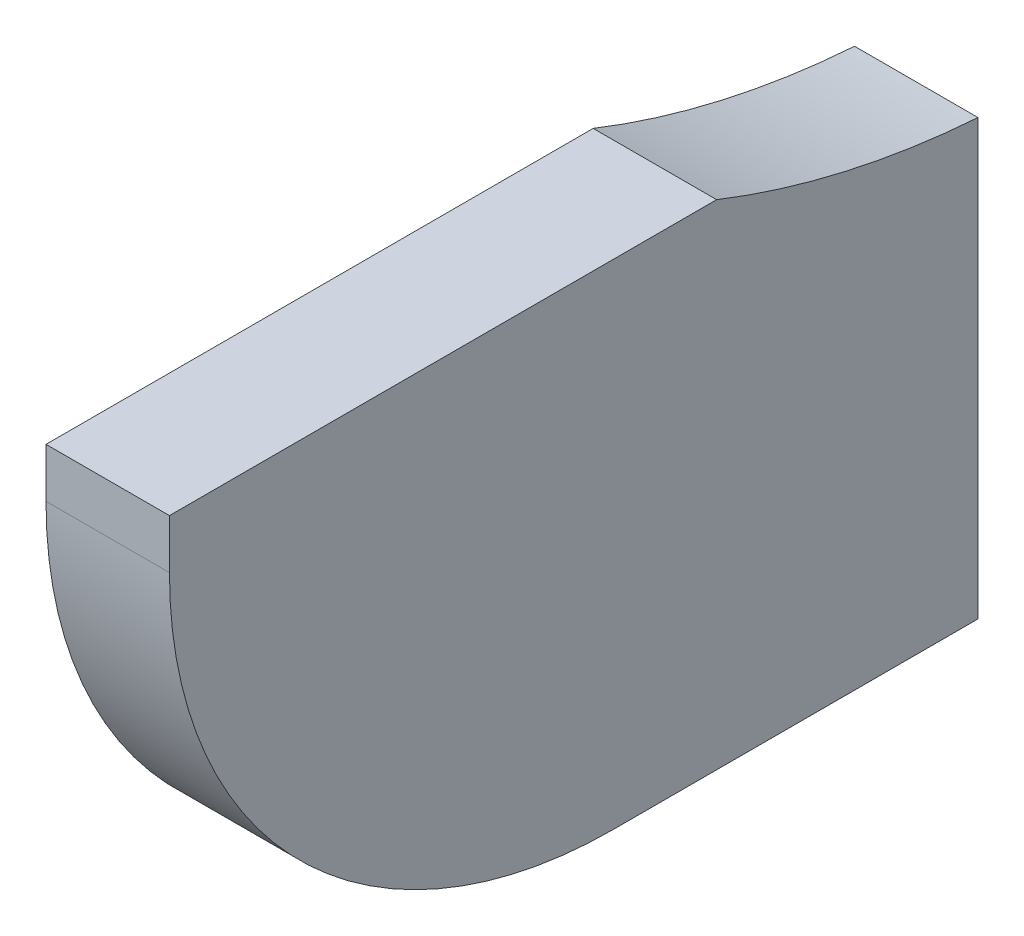
SolidWorks part; units mm, degrees
ref_plane "Front Plane" through (0, 0, 0) normal (0, 0, 1) x (1, 0, 0)
ref_plane "Top Plane" through (0, 0, 0) normal (0, 1, 0) x (1, 0, 0)
ref_plane "Right Plane" through (0, 0, 0) normal (1, 0, 0) x (0, 0, -1)
sketch "Sketch1" plane through (0, 0, 0) normal (0, 0, 1) x (1, 0, 0)
  line L1 (-5, 20) -> (0, 20)
  line L2 (-5, 20) -> (-5, 0)
  line L3 (-5, 0) -> (0, 0)
  line L4 (0, 20) -> (0, 0)
  dimension "D1" = 20
  dimension "D2" = 5
extrude "Boss-Extrude1" add sketch "Sketch1" along normal blind 84.5
sketch "Sketch2" plane through (-5, 0, 0) normal (-1, 0, 0) x (0, 0, 1)
  line L1 (84.5, 0) -> (0, 0)
  line L2 (84.5, 0) -> (84.5, 20)
  line L3 (84.5, 20) -> (0, 20)
  line L4 (0, 0) -> (0, 20)
  line L5 (77.75, 0) -> (6.75, 0)
  line L6 (77.75, 0) -> (77.75, 20)
  line L7 (77.75, 20) -> (6.75, 20)
  line L8 (6.75, 0) -> (6.75, 20)
  line L9 (44.75, 0) -> (39.75, 0)
  line L10 (44.75, 0) -> (44.75, 20)
  line L11 (44.75, 20) -> (39.75, 20)
  line L12 (39.75, 0) -> (39.75, 20)
  dimension "D1" = 71
  dimension "D2" = 6.75
  dimension "D3" = 5
  dimension "D4" = 33
sketch "Sketch5" plane through (0, 0, 0) normal (1, 0, 0) x (0, 0, -1)
  line L0 (-84.5, 0) -> (0, 0) construction
  line L3 (-84.5, 0) -> (-84.5, 20) construction
  circle A0 centre (-42.25, 53) radius 35.5
  dimension "D1" = 71
  dimension "D2" = 53
  dimension "D3" = 42.25
extrude "Cut-Extrude2" cut sketch "Sketch5" against normal blind 35 and the other way blind 35
extrude "Cut-Extrude3" cut sketch "Sketch2" against normal blind 13 contours L12 L5 L10 L7 region at (-5, 10, 42.25)
sketch "Sketch8" plane through (-5, 0, 0) normal (-1, 0, 0) x (0, 0, 1)
  line L1 (39.75, 0) -> (0, 0)
  line L2 (39.75, 0) -> (39.75, 20)
  line L3 (39.75, 20) -> (0, 20)
  line L4 (0, 0) -> (0, 20)
extrude "Cut-Extrude4" cut sketch "Sketch8" against normal blind 13
sketch "Sketch9" plane through (0, 20, 0) normal (0, 1, 0) x (1, 0, 0)
  line L0 (0, -84.5) -> (0, -55.3363) construction
  line L1 (-5, -84.5) -> (0, -84.5)
  line L2 (-5, -84.5) -> (-5, -77.5)
  line L3 (-5, -77.5) -> (0, -77.5)
  line L4 (0, -84.5) -> (0, -77.5)
  dimension "D1" = 7
extrude "Cut-Extrude5" cut sketch "Sketch9" against normal blind 24
fillet "Fillet1" radius 18 1 edges at (-2.5, 0, 77.5)
